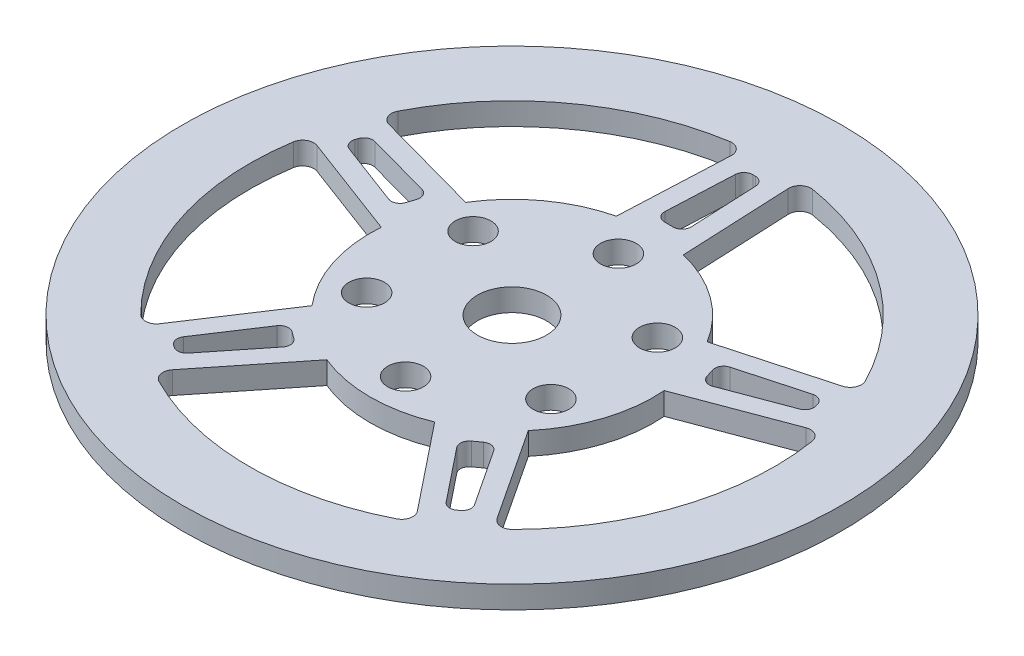
SolidWorks part; units mm, degrees
ref_plane "Front Plane" through (0, 0, 0) normal (0, 0, 1) x (1, 0, 0)
ref_plane "Top Plane" through (0, 0, 0) normal (0, 1, 0) x (1, 0, 0)
ref_plane "Right Plane" through (0, 0, 0) normal (1, 0, 0) x (0, 0, -1)
sketch "Sketch1" plane through (0, 0, 0) normal (0, 1, 0) x (1, 0, 0)
  line L0 (0, 0) -> (0, -9.525) construction
  line L1 (0, 0) -> (8.2489, -4.7625) construction
  line L2 (0, 0) -> (8.2489, 4.7625) construction
  line L3 (0, 0) -> (0, 33.015) construction
  line L4 (0, 0) -> (31.3992, 10.2022) construction
  line L5 (0, 0) -> (19.4058, -26.7097) construction
  line L6 (0, 0) -> (-19.4058, -26.7097) construction
  line L7 (0, 0) -> (-31.3992, 10.2022) construction
  line L8 (-2.5, 23.3666) -> (2.5, 23.3666) construction
  line L9 (-3, 12.3406) -> (3, 12.3406) construction
  line L10 (-2.5, 23.3666) -> (-3, 12.3406)
  line L11 (2.5, 23.3666) -> (3, 12.3406)
  line L12 (-0.8753, 21.6666) -> (0.8753, 21.6666)
  line L13 (0.8753, 21.6666) -> (1.2212, 14.0406)
  line L14 (1.2212, 14.0406) -> (-1.2212, 14.0406)
  line L15 (-1.2212, 14.0406) -> (-0.8753, 21.6666)
  line L16 (21.4505, 9.5983) -> (10.8095, 6.6666)
  line L17 (12.976, 5.5002) -> (20.3357, 7.5279)
  line L18 (20.8767, 5.8629) -> (13.7307, 3.1774)
  line L19 (20.3357, 7.5279) -> (20.8767, 5.8629)
  line L20 (13.7307, 3.1774) -> (12.976, 5.5002)
  line L21 (22.9955, 4.843) -> (12.6636, 0.9603)
  line L22 (15.7571, -17.4345) -> (9.6807, -8.2204)
  line L23 (9.2408, -10.6413) -> (13.4435, -17.0142)
  line L24 (12.0272, -18.0432) -> (7.2649, -12.0769)
  line L25 (13.4435, -17.0142) -> (12.0272, -18.0432)
  line L26 (7.2649, -12.0769) -> (9.2408, -10.6413)
  line L27 (11.712, -20.3735) -> (4.8266, -11.7471)
  line L28 (-11.712, -20.3735) -> (-4.8266, -11.7471)
  line L29 (-7.2649, -12.0769) -> (-12.0272, -18.0432)
  line L30 (-13.4435, -17.0142) -> (-9.2408, -10.6413)
  line L31 (-12.0272, -18.0432) -> (-13.4435, -17.0142)
  line L32 (-9.2408, -10.6413) -> (-7.2649, -12.0769)
  line L33 (-15.7571, -17.4345) -> (-9.6807, -8.2204)
  line L34 (-22.9955, 4.843) -> (-12.6636, 0.9603)
  line L35 (-13.7307, 3.1774) -> (-20.8767, 5.8629)
  line L36 (-20.3357, 7.5279) -> (-12.976, 5.5002)
  line L37 (-20.8767, 5.8629) -> (-20.3357, 7.5279)
  line L38 (-12.976, 5.5002) -> (-13.7307, 3.1774)
  line L39 (-21.4505, 9.5983) -> (-10.8095, 6.6666)
  circle A0 centre (0, 0) radius 12.7 construction
  circle A1 centre (0, 9.525) radius 1.6
  circle A2 centre (-8.2489, 4.7625) radius 1.6
  circle A3 centre (-8.2489, -4.7625) radius 1.6
  circle A4 centre (0, -9.525) radius 1.6
  circle A5 centre (0, 0) radius 29.5
  circle A6 centre (8.2489, 4.7625) radius 1.6
  circle A7 centre (0, 0) radius 3.1
  circle A8 centre (8.2489, -4.7625) radius 1.6
  circle A9 centre (0, 0) radius 23.5 construction
  arc A10 (-3, 12.3406) -> (-10.8095, 6.6666) centre (0, 0) ccw
  arc A11 (10.8095, 6.6666) -> (3, 12.3406) centre (0, 0) ccw
  arc A12 (9.6807, -8.2204) -> (12.6636, 0.9603) centre (0, 0) ccw
  arc A13 (4.8266, -11.7471) -> (-4.8266, -11.7471) centre (0, 0) cw
  arc A14 (-12.6636, 0.9603) -> (-9.6807, -8.2204) centre (0, 0) ccw
  arc A15 (-21.4505, 9.5983) -> (-2.5, 23.3666) centre (0, 0) cw
  arc A16 (2.5, 23.3666) -> (21.4505, 9.5983) centre (0, 0) cw
  arc A17 (22.9955, 4.843) -> (15.7571, -17.4345) centre (0, 0) cw
  arc A18 (11.712, -20.3735) -> (-11.712, -20.3735) centre (0, 0) cw
  arc A19 (-15.7571, -17.4345) -> (-22.9955, 4.843) centre (0, 0) cw
  point P25 (0, 0)
  point P66 (0, 0)
  dimension "D1" = 3.2
  dimension "D2" = 3.2
  dimension "D5" = 59
  dimension "D6" = 47
  dimension "D9" = 25.4
  dimension "D16" = 6.2
  dimension "D17" = 3.2
  dimension "D18" = 3.2
  dimension "D19" = 3.2
  dimension "D20" = 3.2
  dimension "D3" = 60
  dimension "D4" = 60
  dimension "D8" = 2.5
  dimension "D10" = 3
  dimension "D11" = 1.7
  dimension "D13" = 1.7
  dimension "D14" = 1.7
  dimension "D7" = 5
  dimension "D15" = 5
extrude "Boss-Extrude1" add sketch "Sketch1" along normal blind 2
fillet "Fillet2" radius 1 10 edges at (-15.7571, 1, 17.4345) (-11.712, 1, 20.3735) (11.712, 1, 20.3735) (15.7571, 1, 17.4345) (22.9955, 1, -4.843) (21.4505, 1, -9.5983) (2.5, 1, -23.3666) (-2.5, 1, -23.3666) (-22.9955, 1, -4.843) (-21.4505, 1, -9.5983)
fillet "Fillet3" radius 0.8 20 edges at (-20.8767, 1, -5.8629) (-20.3357, 1, -7.5279) (-12.976, 1, -5.5002) (-13.7307, 1, -3.1774) (-12.0272, 1, 18.0432) (-13.4435, 1, 17.0142) (-9.2408, 1, 10.6413) (-7.2649, 1, 12.0769) (13.4435, 1, 17.0142) (12.0272, 1, 18.0432) (7.2649, 1, 12.0769) (9.2408, 1, 10.6413) (12.976, 1, -5.5002) (20.3357, 1, -7.5279) (20.8767, 1, -5.8629) (13.7307, 1, -3.1774) (-0.8753, 1, -21.6666) (0.8753, 1, -21.6666) (-1.2212, 1, -14.0406) (1.2212, 1, -14.0406)
